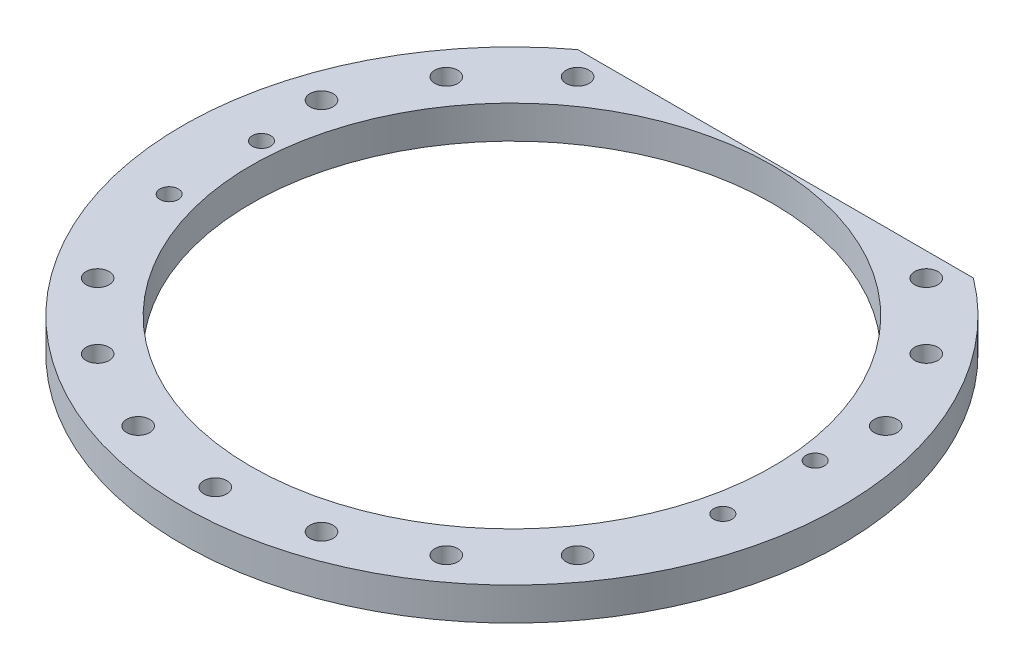
SolidWorks part; units mm, degrees
ref_plane "Front Plane" through (0, 0, 0) normal (0, 0, 1) x (1, 0, 0)
ref_plane "Top Plane" through (0, 0, 0) normal (0, 1, 0) x (1, 0, 0)
ref_plane "Right Plane" through (0, 0, 0) normal (1, 0, 0) x (0, 0, -1)
sketch "Sketch4" plane through (0, 0, 0) normal (0, 1, 0) x (1, 0, 0)
  line L0 (0, -45) -> (0, 45) construction
  line L1 (-7.164, 43.0634) -> (7.164, 43.0634) construction
  line L2 (0, 0) -> (10.9933, 0) construction
  circle A0 centre (0, 0) radius 39.565
  circle A1 centre (0, 0) radius 50
  circle A2 centre (42, -10) radius 1.4
  circle A3 centre (42, 4) radius 1.4
  circle A4 centre (-42, -10) radius 1.4
  circle A5 centre (-42, 4) radius 1.4
  circle A10 centre (0, -45) radius 1.75
  circle A11 centre (-13.9058, -42.7975) radius 1.75
  circle A12 centre (-26.4503, -36.4058) radius 1.75
  circle A13 centre (-36.4058, -26.4503) radius 1.75
  circle A14 centre (-42.7975, -13.9058) radius 1.75 [skipped]
  circle A15 centre (-45, 0) radius 1.75 [skipped]
  circle A16 centre (-42.7975, 13.9058) radius 1.75
  circle A17 centre (-36.4058, 26.4503) radius 1.75
  circle A18 centre (-26.4503, 36.4058) radius 1.75
  circle A19 centre (-13.9058, 42.7975) radius 1.75 [skipped]
  circle A20 centre (0, 45) radius 1.75 [skipped]
  circle A21 centre (13.9058, 42.7975) radius 1.75 [skipped]
  circle A22 centre (26.4503, 36.4058) radius 1.75
  circle A23 centre (36.4058, 26.4503) radius 1.75
  circle A24 centre (42.7975, 13.9058) radius 1.75
  circle A25 centre (45, 0) radius 1.75 [skipped]
  circle A26 centre (42.7975, -13.9058) radius 1.75 [skipped]
  circle A27 centre (36.4058, -26.4503) radius 1.75
  circle A28 centre (26.4503, -36.4058) radius 1.75
  circle A29 centre (13.9058, -42.7975) radius 1.75
  point P5 (0, 0)
  point P19 (0, 43.0634)
  point P61 (0, 0)
  dimension "D1" = 79.13
  dimension "D3" = 100
  dimension "D4" = 2.8
  dimension "D5" = 3.5
  dimension "D2" = 90
  dimension "D6" = 20
extrude "Boss-Extrude3" add sketch "Sketch4" along normal blind 5
sketch "Sketch6" plane through (0, 0, 0) normal (1, 0, 0) x (0, 0, -1)
  line L0 (-50, 5) -> (-79.0628, 53)
  line L2 (-50, 5) -> (-39.565, 5)
  line L3 (-39.565, 5) -> (-68.6278, 53)
  line L5 (-68.6278, 53) -> (-79.0628, 53)
  dimension "D1" = 18.6278
  dimension "D2" = 48
ref_plane "Plane1" through (0, 15, 0) normal (0, 1, 0) x (1, 0, 0)
ref_axis "Axis1" through (0, 0, 0) along (0, 1, 0)
sketch "Sketch8" plane through (0, 0, 0) normal (0, -1, 0) x (1, 0, 0)
  circle A0 centre (42, 10) radius 2.5
  circle A1 centre (42, -4) radius 2.5
  circle A2 centre (-42, 10) radius 2.5
  circle A3 centre (-42, -4) radius 2.5
  dimension "D1" = 5
sketch "Sketch10" plane through (0, 0, 0) normal (0, 0, 1) x (1, 0, 0)
  line L1 (-59.3818, 22.122) -> (59.6206, 22.122)
  line L2 (-59.3818, 22.122) -> (-59.3818, -9.6385)
  line L3 (-59.3818, -9.6385) -> (59.6206, -9.6385)
  line L4 (59.6206, 22.122) -> (59.6206, -9.6385)
  line L5 (-59.3818, 22.122) -> (59.6206, -9.6385) construction
  line L6 (-59.3818, -9.6385) -> (59.6206, 22.122) construction
  point P4 (0.1194, 6.2417)
extrude "Cut-Extrude1" cut sketch "Sketch10" against normal through all from offset 40 offset against normal yes
